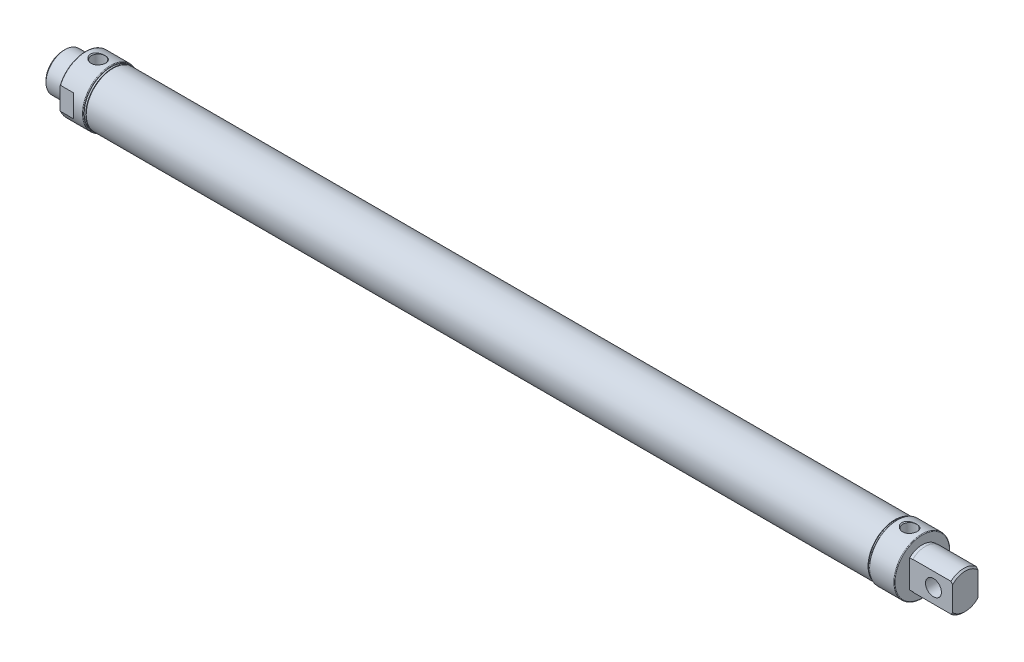
SolidWorks part; units mm, degrees
ref_plane "前视基准面" through (0, 0, 0) normal (0, 0, 1) x (1, 0, 0)
ref_plane "上视基准面" through (0, 0, 0) normal (0, 1, 0) x (1, 0, 0)
ref_plane "右视基准面" through (0, 0, 0) normal (1, 0, 0) x (0, 0, -1)
sketch "草图1" plane through (0, 0, 0) normal (0, 0, 1) x (1, 0, 0)
  line L0 (0, 0) -> (0, 10.773)
  line L1 (0, 10.773) -> (1.227, 12)
  line L2 (1.227, 12) -> (14, 12)
  line L3 (14, 12) -> (14, 17.1)
  line L4 (14.4, 17.5) -> (29.6, 17.5)
  line L5 (30, 17.1) -> (30, 16.8)
  line L6 (30, 16.8) -> (31, 16.8)
  line L7 (31, 16.8) -> (31, 16.3)
  line L8 (31, 16.3) -> (31.3, 16.8)
  line L9 (31.3, 16.8) -> (522.7, 16.8)
  line L10 (522.7, 16.8) -> (523, 16.3)
  line L11 (523, 16.3) -> (523, 16.8)
  line L12 (523, 16.8) -> (524, 16.8)
  line L13 (524, 16.8) -> (524, 17.1)
  line L14 (524.4, 17.5) -> (539.6, 17.5)
  line L15 (540, 17.1) -> (540, 0)
  line L16 (540, 0) -> (0, 0)
  line L17 (540, 0) -> (0, 0) construction
  arc A0 (14, 17.1) -> (14.4, 17.5) centre (14.4, 17.1) cw
  arc A1 (29.6, 17.5) -> (30, 17.1) centre (29.6, 17.1) cw
  arc A2 (524, 17.1) -> (524.4, 17.5) centre (524.4, 17.1) cw
  arc A3 (539.6, 17.5) -> (540, 17.1) centre (539.6, 17.1) cw
revolve "旋转1" add sketch "草图1" angle 360 about L17 reverse direction yes
cosmetic thread "装饰螺纹线1" parameters "D1"=12, "D2"=21.546
sketch "草图2" plane through (0, 0, 0) normal (0, 0, 1) x (1, 0, 0)
  line L0 (540, 0) -> (540, 11.85)
  line L1 (540, 11.85) -> (542, 11.85)
  line L2 (542, 11.85) -> (542, 12)
  line L3 (542, 12) -> (566, 12)
  line L4 (566, 12) -> (567, 11)
  line L5 (567, 11) -> (567, 0)
  line L6 (567, 0) -> (540, 0)
  line L7 (567, 0) -> (540, 0) construction
revolve "旋转2" add sketch "草图2" angle 360 about L7 reverse direction yes
cosmetic thread "装饰螺纹线2" parameters "D1"=25, "D2"=20.319
ref_plane "基准面4" through (14, 0, 0) normal (1, 0, 0) x (0, 0, -1)
ref_plane "基准面5" through (567, 0, 0) normal (1, 0, 0) x (0, 0, -1)
sketch "草图3" plane through (567, 0, 0) normal (1, 0, 0) x (0, 0, -1)
  line L0 (-18, 22) -> (-18, -22)
  line L1 (-18, -22) -> (18, -22)
  line L2 (18, -22) -> (18, 22)
  line L3 (18, 22) -> (-18, 22)
  line L4 (-8, 12) -> (-8, -12)
  line L5 (-8, -12) -> (8, -12)
  line L6 (8, -12) -> (8, 12)
  line L7 (8, 12) -> (-8, 12)
extrude "切除-拉伸1" cut sketch "草图3" against normal blind 27
ref_plane "基准面6" through (555, 0, 0) normal (1, 0, 0) x (0, 0, -1)
sketch "草图4" plane through (555, 0, 0) normal (1, 0, 0) x (0, 0, -1)
  line L0 (-8, 0) -> (-8, 5)
  line L1 (-8, 5) -> (8, 5)
  line L2 (8, 5) -> (8, 0)
  line L3 (8, 0) -> (-8, 0)
  line L4 (8, 0) -> (-8, 0) construction
revolve "切除-旋转1" cut sketch "草图4" angle 360 about L4 reverse direction yes
sketch "草图5" plane through (0, 0, 0) normal (0, 0, 1) x (1, 0, 0)
  line L0 (22, 17.5) -> (26.864, 17.5)
  line L1 (26.864, 17.5) -> (26.283, 16.919)
  line L2 (26.283, 16.919) -> (26.283, 9.5)
  line L3 (26.283, 9.5) -> (22, 9.5)
  line L4 (22, 9.5) -> (22, 17.5)
  line L5 (22, 9.5) -> (22, 17.5) construction
revolve "切除-旋转2" cut sketch "草图5" angle 360 about L5 reverse direction yes
cosmetic thread "装饰螺纹线3" parameters "D1"=8, "D2"=9.728
sketch "草图6" plane through (0, 0, 0) normal (0, 0, 1) x (1, 0, 0)
  line L0 (532, 17.5) -> (536.864, 17.5)
  line L1 (536.864, 17.5) -> (536.283, 16.919)
  line L2 (536.283, 16.919) -> (536.283, 9.5)
  line L3 (536.283, 9.5) -> (532, 9.5)
  line L4 (532, 9.5) -> (532, 17.5)
  line L5 (532, 9.5) -> (532, 17.5) construction
revolve "切除-旋转3" cut sketch "草图6" angle 360 about L5 reverse direction yes
cosmetic thread "装饰螺纹线4" parameters "D1"=8, "D2"=9.728
sketch "草图7" plane through (0, 0, 0) normal (0, 1, 0) x (1, 0, 0)
  line L0 (-4, -17.5) -> (24, -17.5)
  line L1 (24, -17.5) -> (22.5, -16)
  line L2 (22.5, -16) -> (-2, -16)
  line L3 (-2, -16) -> (-2, 16)
  line L4 (-2, 16) -> (22.5, 16)
  line L5 (22.5, 16) -> (24, 17.5)
  line L6 (24, 17.5) -> (-4, 17.5)
  line L7 (-4, 17.5) -> (-4, -17.5)
extrude "切除-拉伸2" cut sketch "草图7" along normal blind 35 and the other way blind 35
sketch "草图8" plane through (0, 0, 0) normal (0, 0, 1) x (1, 0, 0)
  line L0 (0, 0) -> (0, 6)
  line L1 (0, 6) -> (41, 6)
  line L2 (41, 6) -> (41, 16)
  line L3 (41, 16) -> (513, 16)
  line L4 (513, 16) -> (513, 0)
  line L5 (513, 0) -> (0, 0)
  line L6 (513, 0) -> (0, 0) construction
revolve "切除-旋转4" cut sketch "草图8" angle 360 about L6 reverse direction yes
ref_plane "基准面7" through (22, 0, 0) normal (1, 0, 0) x (0, 0, -1)
ref_plane "基准面8" through (0, 20.8, 0) normal (0, 1, 0) x (1, 0, 0)
ref_plane "基准面9" through (532, 0, 0) normal (1, 0, 0) x (0, 0, -1)
ref_plane "基准面10" through (6, 0, 0) normal (1, 0, 0) x (0, 0, -1)
ref_plane "基准面11" through (30, 0, 0) normal (1, 0, 0) x (0, 0, -1)
ref_plane "基准面12" through (14, 0, 0) normal (1, 0, 0) x (0, 0, -1)
ref_plane "基准面13" through (540, 0, 0) normal (1, 0, 0) x (0, 0, -1)
ref_plane "基准面14" through (548, 0, 0) normal (1, 0, 0) x (0, 0, -1)
ref_plane "基准面15" through (31, 0, 0) normal (1, 0, 0) x (0, 0, -1)
ref_plane "基准面16" through (523, 0, 0) normal (1, 0, 0) x (0, 0, -1)
ref_plane "IP_SWITCH1 XY" through (31, 0, 0) normal (-1, 0, 0) x (0, 0, 1)
ref_plane "IP_SWITCH1 XZ" through (0, 0, 0) normal (0, 1, 0) x (1, 0, 0)
ref_plane "IP_SWITCH1 YZ" through (0, 0, 0) normal (0, 0, -1) x (-1, 0, 0)
ref_axis "IP_SWITCH1 X" through (31, 0, 80.9) along (0, 0, -1)
ref_axis "IP_SWITCH1 Y" through (31, 50, 0) along (0, -1, 0)
ref_axis "IP_SWITCH1 Z" through (-80.9, 0, 0) along (1, 0, 0)
sketch3d "IP_SWITCH1"
  point P0 (31, 0, 0)
ref_plane "IP_SWITCH2 XY" through (523, 0, 0) normal (1, 0, 0) x (0, 0, -1)
ref_plane "IP_SWITCH2 XZ" through (0, 0, 0) normal (0, -1, 0) x (-1, 0, 0)
ref_plane "IP_SWITCH2 YZ" through (0, 0, 0) normal (0, 0, -1) x (-1, 0, 0)
ref_axis "IP_SWITCH2 X" through (523, 0, 80.9) along (0, 0, -1)
ref_axis "IP_SWITCH2 Y" through (523, -50, 0) along (0, 1, 0)
ref_axis "IP_SWITCH2 Z" through (80.9, 0, 0) along (-1, 0, 0)
sketch3d "IP_SWITCH2"
  point P0 (523, 0, 0)
ref_plane "body-dummy XY" through (30, 0, 0) normal (1, 0, 0) x (0, 0, -1)
ref_plane "body-dummy XZ" through (0, 0, 0) normal (0, -1, 0) x (-1, 0, 0)
ref_plane "body-dummy YZ" through (0, 0, 0) normal (0, 0, -1) x (-1, 0, 0)
ref_axis "body-dummy X" through (30, 0, 80.9) along (0, 0, -1)
ref_axis "body-dummy Y" through (30, -50, 0) along (0, 1, 0)
ref_axis "body-dummy Z" through (80.9, 0, 0) along (-1, 0, 0)
sketch3d "body-dummy"
  point P0 (30, 0, 0)
ref_plane "body-sdb XY" through (0, 0, 0) normal (0, 0, 1) x (1, 0, 0)
ref_plane "body-sdb XZ" through (0, 0, 0) normal (0, -1, 0) x (-1, 0, 0)
ref_plane "body-sdb YZ" through (555, 0, 0) normal (1, 0, 0) x (0, 0, -1)
ref_axis "body-sdb X" through (-80.9, 0, 0) along (1, 0, 0)
ref_axis "body-sdb Y" through (555, -50, 0) along (0, 1, 0)
ref_axis "body-sdb Z" through (555, 0, 80.9) along (0, 0, -1)
sketch3d "body-sdb"
  point P0 (555, 0, 0)
ref_plane "fa-body XY" through (14, 0, 0) normal (-1, 0, 0) x (0, 0, 1)
ref_plane "fa-body XZ" through (0, 0, 0) normal (0, 1, 0) x (1, 0, 0)
ref_plane "fa-body YZ" through (0, 0, 0) normal (0, 0, -1) x (-1, 0, 0)
ref_axis "fa-body X" through (14, 0, 80.9) along (0, 0, -1)
ref_axis "fa-body Y" through (14, 50, 0) along (0, -1, 0)
ref_axis "fa-body Z" through (-80.9, 0, 0) along (1, 0, 0)
sketch3d "fa-body"
  point P0 (14, 0, 0)
ref_plane "lb-body XY" through (540, 0, 0) normal (1, 0, 0) x (0, 0, -1)
ref_plane "lb-body XZ" through (0, 0, 0) normal (0, -1, 0) x (-1, 0, 0)
ref_plane "lb-body YZ" through (0, 0, 0) normal (0, 0, -1) x (-1, 0, 0)
ref_axis "lb-body X" through (540, 0, 80.9) along (0, 0, -1)
ref_axis "lb-body Y" through (540, -50, 0) along (0, 1, 0)
ref_axis "lb-body Z" through (80.9, 0, 0) along (-1, 0, 0)
sketch3d "lb-body"
  point P0 (540, 0, 0)
ref_plane "nut1-body XY" through (548, 0, 0) normal (1, 0, 0) x (0, 0, -1)
ref_plane "nut1-body XZ" through (0, 0, 0) normal (0, -1, 0) x (-1, 0, 0)
ref_plane "nut1-body YZ" through (0, 0, 0) normal (0, 0, -1) x (-1, 0, 0)
ref_axis "nut1-body X" through (548, 0, 80.9) along (0, 0, -1)
ref_axis "nut1-body Y" through (548, -50, 0) along (0, 1, 0)
ref_axis "nut1-body Z" through (80.9, 0, 0) along (-1, 0, 0)
sketch3d "nut1-body"
  point P0 (548, 0, 0)
ref_plane "nut2-body XY" through (6, 0, 0) normal (-1, 0, 0) x (0, 0, 1)
ref_plane "nut2-body XZ" through (0, 0, 0) normal (0, 1, 0) x (1, 0, 0)
ref_plane "nut2-body YZ" through (0, 0, 0) normal (0, 0, -1) x (-1, 0, 0)
ref_axis "nut2-body X" through (6, 0, 80.9) along (0, 0, -1)
ref_axis "nut2-body Y" through (6, 50, 0) along (0, -1, 0)
ref_axis "nut2-body Z" through (-80.9, 0, 0) along (1, 0, 0)
sketch3d "nut2-body"
  point P0 (6, 0, 0)
ref_plane "rod-body XY" through (0, 0, 0) normal (-1, 0, 0) x (0, 0, 1)
ref_plane "rod-body XZ" through (0, 0, 0) normal (0, 1, 0) x (1, 0, 0)
ref_plane "rod-body YZ" through (0, 0, 0) normal (0, 0, -1) x (-1, 0, 0)
ref_axis "rod-body X" through (0, 0, 80.9) along (0, 0, -1)
ref_axis "rod-body Y" through (0, 50, 0) along (0, -1, 0)
ref_axis "rod-body Z" through (-80.9, 0, 0) along (1, 0, 0)
sketch3d "rod-body"
  point P0 (0, 0, 0)
ref_plane "rod-nut XY" through (0, 0, 0) normal (-1, 0, 0) x (0, 0, 1)
ref_plane "rod-nut XZ" through (0, 0, 0) normal (0, 1, 0) x (1, 0, 0)
ref_plane "rod-nut YZ" through (0, 0, 0) normal (0, 0, -1) x (-1, 0, 0)
ref_axis "rod-nut X" through (0, 0, 80.9) along (0, 0, -1)
ref_axis "rod-nut Y" through (0, 50, 0) along (0, -1, 0)
ref_axis "rod-nut Z" through (-80.9, 0, 0) along (1, 0, 0)
sketch3d "rod-nut"
  point P0 (0, 0, 0)
